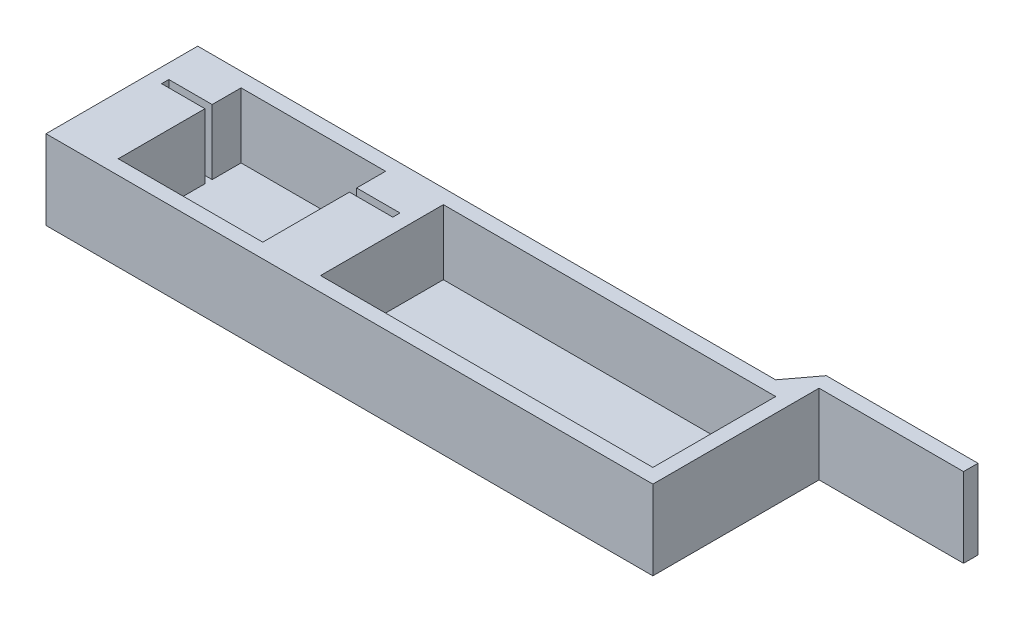
SolidWorks part; units mm, degrees
ref_plane "Front Plane" through (0, 0, 0) normal (0, 0, 1) x (1, 0, 0)
ref_plane "Top Plane" through (0, 0, 0) normal (0, 1, 0) x (1, 0, 0)
ref_plane "Right Plane" through (0, 0, 0) normal (1, 0, 0) x (0, 0, -1)
sketch "Sketch1" plane through (0, 0, 0) normal (0, 1, 0) x (1, 0, 0)
  line L0 (0, 0) -> (40, 0) construction
  line L1 (0, 0) -> (-40, 0) construction
  line L2 (40, -8.5) -> (40, 8.5)
  line L3 (40, 8.5) -> (-40, 8.5)
  line L4 (-40, 8.5) -> (-40, -8.5)
  line L5 (-40, -8.5) -> (40, -8.5)
  line L6 (40, 8.5) -> (40, 10.5) construction
  line L7 (40, 10.5) -> (42, 10.5) construction
  line L8 (-40, -8.5) -> (-40, -10.5) construction
  line L9 (-40, -10.5) -> (-42, -10.5) construction
  line L10 (-40, 0) -> (-34, 0) construction
  line L11 (-42, -10.5) -> (42, -10.5)
  line L12 (-42, -10.5) -> (-42, 10.5)
  line L13 (-42, 10.5) -> (42, 10.5)
  line L14 (42, -10.5) -> (42, 10.5)
  line L15 (-34, 0) -> (-14, 0) construction
  line L16 (-34, -8.5) -> (-34, 3.5)
  line L17 (-34, 3.5) -> (-40, 3.5)
  line L18 (-40, 3.5) -> (-40, 4.4487)
  line L19 (-34, 4.5) -> (-40, 4.5)
  line L20 (-34, 4.5) -> (-34, 8.5)
  line L21 (-14, 3.5) -> (-14, -8.5)
  line L22 (-14, 3.5) -> (-8, 3.5)
  line L23 (-8, 3.5) -> (-8, 4.5)
  line L24 (-8, 4.5) -> (-14, 4.5)
  line L25 (-14, 4.5) -> (-14, 8.5)
  line L26 (-8, 3.5) -> (-6, 3.5) construction
  line L27 (-6, 8.5) -> (-6, -8.5)
  line L28 (62, 12.5) -> (42, 12.5)
  line L29 (42, 12.5) -> (42, 10.5)
  line L30 (62, 14.5) -> (41, 14.5)
  line L31 (62, 13.5) -> (62, 12.5)
  line L32 (62, 12.5) -> (62, 14.5)
  line L33 (40, 10.5) -> (38, 10.5) construction
  line L34 (38, 10.5) -> (41, 14.5)
  point P7 (40, 0)
extrude "Boss-Extrude1" add sketch "Sketch1" along normal blind 2 contours L34 L13 L29 L28 L31 L32 L30 | L3 L27 L5 L2 | L27 L3 L25 L24 L23 L22 L21 L5 | L19 L20 L3 L4 | L24 L25 L3 L20 L19 L4 L17 L16 L5 L21 L22 L23 | L16 L17 L4 L5 | L11 L14 L13 L12 L5 L4 L3 L2 region at (17, 0, 0) region at (-9.9538, 0, 0.1846) region at (-24, 0, -0.1364) region at (-37, 0, 2.5) region at (-37, 0, -6.5) region at (-41.1341, 0, 0) region at (49.72, 0, -13.22)
extrude "Boss-Extrude2" add sketch "Sketch1<4>" along normal blind 11 contours L34 L13 L29 L28 L31 L32 L30 | L11 L14 L13 L12 L5 L4 L3 L2 | L27 L3 L25 L24 L23 L22 L21 L5 | L16 L17 L4 L5 | L19 L20 L3 L4 region at (-9.9538, 0, 0.1846) region at (-37, 0, 2.5) region at (-37, 0, -6.5) region at (-41.1341, 0, 0) region at (49.72, 0, -13.22)
sketch "Sketch1<4>" plane through (0, 0, 0) normal (0, 1, 0) x (1, 0, 0) same geometry as "Sketch1"
